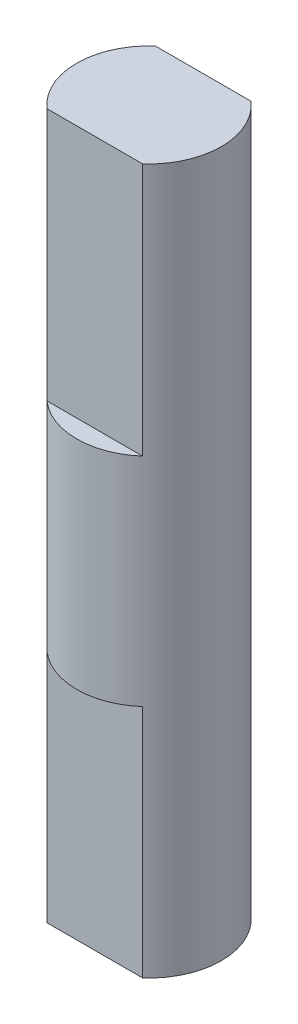
SolidWorks part; units mm, degrees
ref_plane "Alzado" through (0, 0, 0) normal (0, 0, 1) x (1, 0, 0)
ref_plane "Planta" through (0, 0, 0) normal (0, 1, 0) x (1, 0, 0)
ref_plane "Vista lateral" through (0, 0, 0) normal (1, 0, 0) x (0, 0, -1)
sketch "Croquis1" plane through (0, 0, 0) normal (0, 1, 0) x (1, 0, 0)
  circle A2 centre (0, 0) radius 4
  dimension "D1" = 8
extrude "Saliente-Extruir1" add sketch "Croquis1" along normal blind 12
sketch "Croquis2" plane through (0, 12, 0) normal (0, 1, 0) x (1, 0, 0)
  line L1 (-2.6458, -3) -> (2.6458, -3)
  line L3 (-2.6458, 3) -> (2.6458, 3)
  line L5 (-3.4581, -2.0104) -> (3.4581, 2.0104) construction
  line L6 (-3.4581, 2.0104) -> (3.4581, -2.0104) construction
  arc A0 (2.6458, -3) -> (2.6458, 3) centre (0, 0) ccw
  arc A1 (-2.6458, 3) -> (-2.6458, -3) centre (0, 0) ccw
extrude "Saliente-Extruir2" add sketch "Croquis2" along normal blind 14 and the other way blind 25
